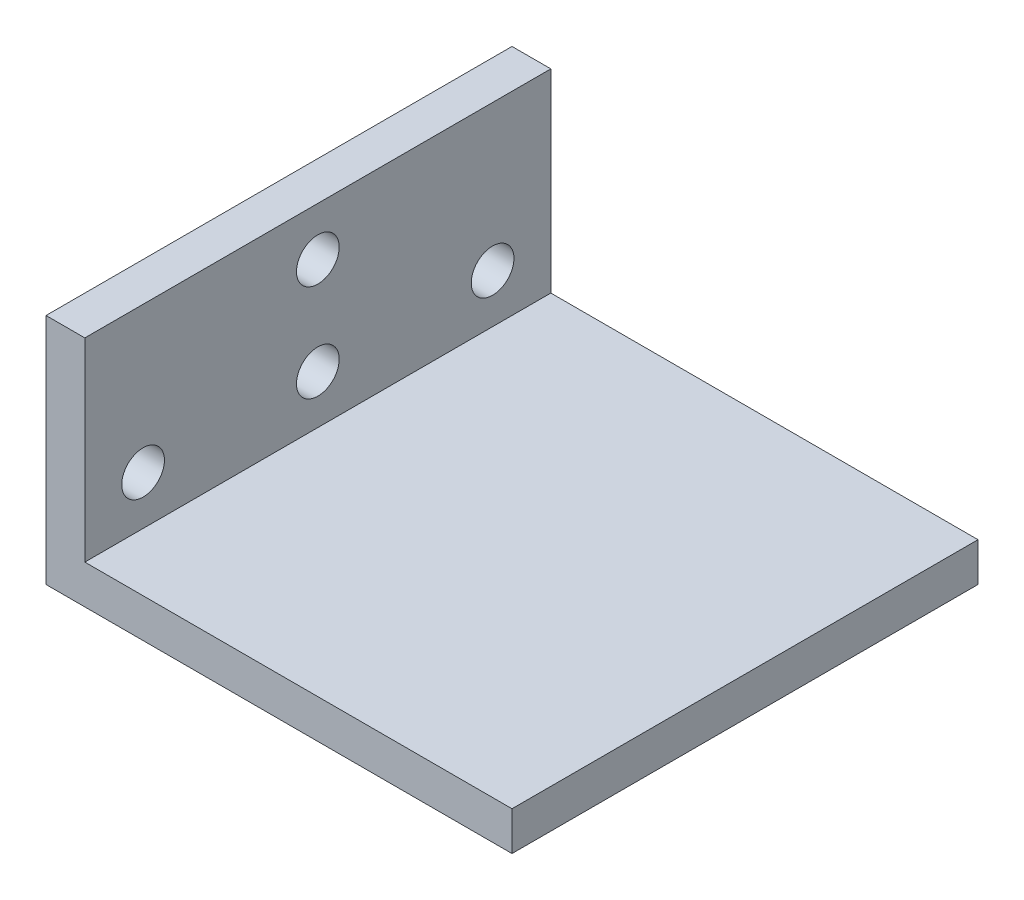
SolidWorks part; units mm, degrees
material "AISI 1015 Steel, Cold Drawn (SS)"
ref_plane "Front Plane" through (0, 0, 0) normal (0, 0, 1) x (1, 0, 0)
ref_plane "Top Plane" through (0, 0, 0) normal (0, 1, 0) x (1, 0, 0)
ref_plane "Right Plane" through (0, 0, 0) normal (1, 0, 0) x (0, 0, -1)
sketch "Sketch1" plane through (0, 0, 0) normal (0, 0, 1) x (1, 0, 0)
  line L0 (0, 0) -> (0, 76.2)
  line L1 (0, 76.2) -> (12.7, 76.2)
  line L2 (12.7, 76.2) -> (12.7, 12.7)
  line L3 (12.7, 12.7) -> (152.4, 12.7)
  line L4 (152.4, 12.7) -> (152.4, 0)
  line L5 (152.4, 0) -> (0, 0)
  dimension "D1" = 76.2
  dimension "D2" = 152.4
  dimension "D3" = 12.7
sketch "Sketch2" plane through (0, 0, 0) normal (0, 1, 0) x (1, 0, 0)
  line L0 (0, 0) -> (0, -152.4)
  dimension "D1" = 152.4
  dimension "D2" = 152.4
sweep "Sweep1" add profiles "Sketch1" path "Sketch2"
sketch "Sketch4" plane through (0, 0, 0) normal (0, -1, 0) x (1, 0, 0)
  line L0 (12.7, 152.4) -> (12.7, 0) construction
  line L1 (0, 152.4) -> (152.4, 152.4) construction
  line L2 (0, 0) -> (152.4, 0) construction
  line L3 (12.7, 0) -> (12.7, 152.4) construction
  line L4 (12.7, -10.5833) -> (152.4, -10.5833) construction
  line L5 (152.4, 0) -> (152.4, 152.4) construction
  line L6 (152.4, -10.5833) -> (12.7, 152.4) construction
  line L7 (31.75, 130.175) -> (31.75, -22.225) construction
  line L8 (57.15, 100.5417) -> (57.15, -51.8583) construction
  line L9 (152.4, -162.9833) -> (12.7, 0) construction
  line L10 (152.4, -10.5833) -> (152.4, -162.9833) construction
  line L11 (12.7, -48.6833) -> (31.75, -48.6833) construction
  line L12 (31.75, -48.6833) -> (57.15, -48.6833) construction
  line L13 (57.15, -48.6833) -> (152.4, -48.6833) construction
  circle A1 centre (44.45, -48.6833) radius 12.7
  circle A2 centre (82.55, -10.5833) radius 12.7
  point P23 (57.15, -10.5833)
  point P24 (69.85, -10.5833)
  dimension "D3" = 19.05
  dimension "D1" = 38.1
  dimension "D2" = 49.399
  dimension "D4" = 25.4
  dimension "D5" = 19.05
extrude "Cut-Extrude1" [suppressed] cut sketch "Sketch4" against normal through all
sketch "Sketch5" plane through (0, 0, 0) normal (0, -1, 0) x (-1, 0, 0)
  line L0 (-215.9, 0) -> (-215.9, -152.4) construction
  line L1 (-152.4, 0) -> (-215.9, 0) construction
  line L2 (-152.4, 0) -> (-152.4, -152.4) construction
  line L3 (-152.4, -152.4) -> (-12.7, -152.4) construction
  line L4 (-215.9, -74.0833) -> (-152.4, -74.0833) construction
  line L5 (-107.95, -93.1333) -> (-133.35, -93.1333) construction
  line L6 (-152.4, -74.0833) -> (-215.9, 0) construction
  line L7 (-196.85, -22.225) -> (-196.85, -174.625) construction
  line L8 (-171.45, -51.8583) -> (-171.45, -204.2583) construction
  line L9 (-152.4, -226.4833) -> (-215.9, -152.4) construction
  line L10 (-152.4, -74.0833) -> (-152.4, -226.4833) construction
  line L11 (-215.9, -93.1333) -> (-196.85, -93.1333) construction
  line L12 (-196.85, -93.1333) -> (-171.45, -93.1333) construction
  line L13 (-171.45, -93.1333) -> (-152.4, -93.1333) construction
  line L14 (-31.75, -74.0833) -> (-57.15, -74.0833) construction
  circle A10 centre (-120.65, -93.1333) radius 12.7
  circle A11 centre (-44.45, -74.0833) radius 12.7
  point P23 (-171.45, -74.0833)
  point P24 (-196.85, -74.0833)
  dimension "D1" = 19.05
  dimension "D2" = 49.399
  dimension "D4" = 74.0833
  dimension "D5" = 152.4
  dimension "D6" = 25.4
extrude "Cut-Extrude2" [suppressed] cut sketch "Sketch5" against normal blind 152.4 contours A10 | A10 | A11
sketch "Sketch7" plane through (12.7, 0, 0) normal (1, 0, 0) x (0, 0, -1)
  line L0 (-133.35, 76.2) -> (-133.35, 60.325) construction
  line L1 (0, 76.2) -> (-152.4, 76.2) construction
  line L2 (-133.35, 60.325) -> (-152.4, 60.325) construction
  line L3 (-152.4, 12.7) -> (-152.4, 76.2) construction
  line L4 (-133.35, 60.325) -> (-19.05, 60.325) construction
  line L5 (-19.05, 60.325) -> (-19.05, 28.575) construction
  line L6 (-19.05, 28.575) -> (-133.35, 28.575) construction
  line L7 (-133.35, 28.575) -> (-133.35, 60.325) construction
  line L8 (-19.05, 60.325) -> (0, 60.325) construction
  line L9 (0, 12.7) -> (0, 76.2) construction
  circle A0 centre (-133.35, 60.325) radius 6.985
  circle A1 centre (-133.35, 28.575) radius 6.985
  circle A2 centre (-19.05, 28.575) radius 6.985
  circle A3 centre (-19.05, 60.325) radius 6.985
  circle A4 centre (-76.2, 60.325) radius 6.985
  circle A5 centre (-76.2, 28.575) radius 6.985
  dimension "D1" = 13.97
  dimension "D2" = 15.875
  dimension "D3" = 19.05
  dimension "D4" = 31.75
  dimension "D5" = 114.3
  dimension "D6" = 19.05
extrude "Cut-Extrude4" cut sketch "Sketch7" against normal up to surface (12.7 mm away) contours A2 | A4 | A1 | A5 region at (12.7, 28.575, 133.35) region at (12.7, 28.575, 19.05) region at (12.7, 60.325, 76.2) region at (12.7, 28.575, 76.2) up to face at (0, 38.1, 76.2)
sketch "Sketch8" [suppressed] plane through (19.05, 0, 0) normal (1, 0, 0) x (0, 0, -1)
  line L7 (-25.4, 19.05) -> (-25.4, 38.1) construction
  line L8 (0, 19.05) -> (-50.8, 19.05) construction
  line L9 (-25.4, 38.1) -> (-25.4, 76.2) construction
  line L10 (-25.4, 76.2) -> (-25.4, 95.25) construction
  line L11 (0, 95.25) -> (-50.8, 95.25) construction
  line L12 (-44.45, 38.1) -> (-6.35, 38.1) construction
  line L13 (-44.45, 76.2) -> (-6.35, 76.2) construction
  line L14 (-44.45, 76.2) -> (-50.8, 76.2) construction
  line L15 (-50.8, 19.05) -> (-50.8, 95.25) construction
  line L16 (-6.35, 76.2) -> (0, 76.2) construction
  line L17 (0, 19.05) -> (0, 95.25) construction
  circle A4 centre (-44.45, 76.2) radius 6.985
  circle A5 centre (-6.35, 76.2) radius 6.985
  circle A6 centre (-6.35, 38.1) radius 6.985
  circle A7 centre (-44.45, 38.1) radius 6.985
  point P25 (-25.4, 38.1)
  point P28 (-25.4, 76.2)
  dimension "D4" = 13.97
  dimension "D1" = 19.05
  dimension "D2" = 38.1
extrude "Cut-Extrude5" [suppressed] cut sketch "Sketch8" against normal up to surface (19.05 mm away) contours A4 | A6 | A7 | A5
sketch "Sketch9" [suppressed] plane through (0, 19.05, 0) normal (0, 1, 0) x (1, 0, 0)
  line L0 (152.4, 0) -> (76.2, 0)
  line L1 (152.4, 0) -> (0, 0) construction
  line L2 (76.2, 0) -> (76.2, -76.2)
  line L3 (152.4, -76.2) -> (19.05, -76.2) construction
  line L4 (76.2, -76.2) -> (152.4, -76.2)
  line L5 (152.4, -76.2) -> (152.4, 0)
  dimension "D1" = 76.2
extrude "Cut-Extrude6" [suppressed] cut sketch "Sketch9" against normal up to surface (19.05 mm away)
fillet "Fillet1" [suppressed] radius 1.27
